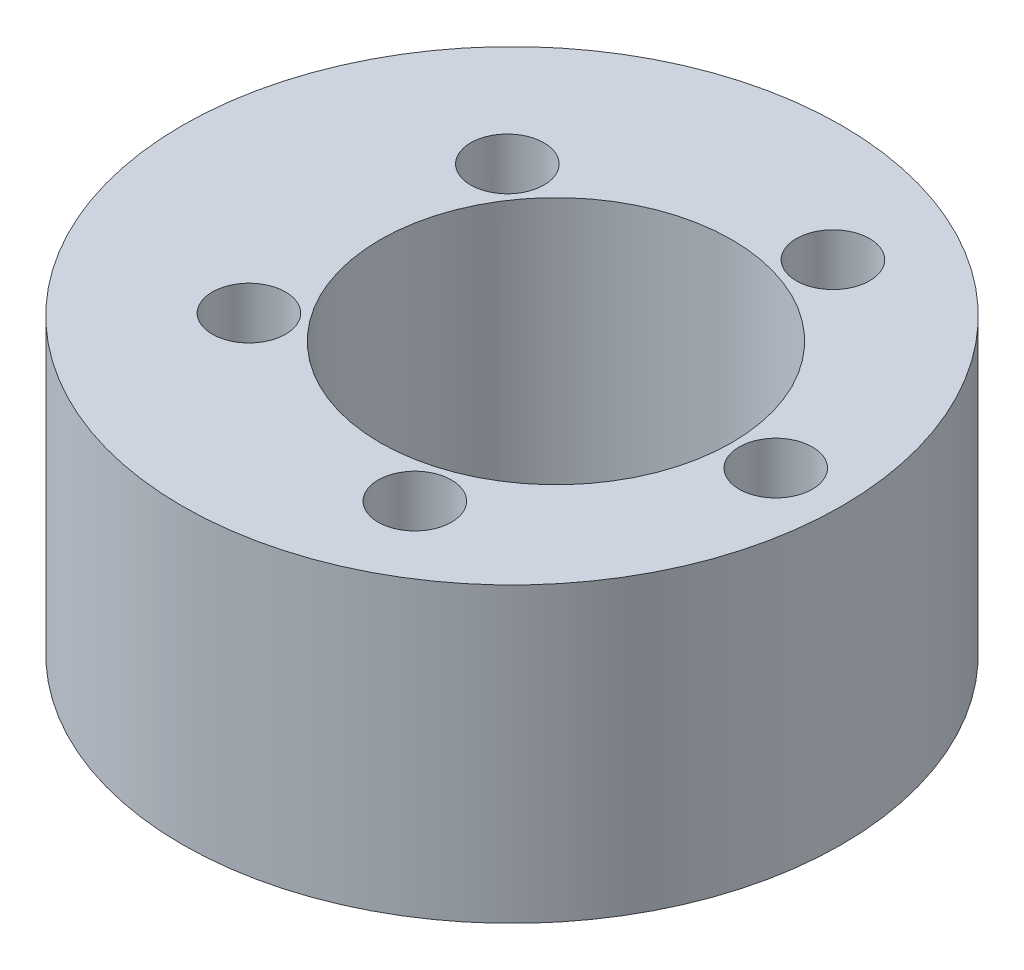
SolidWorks part; units mm, degrees
ref_plane "Front Plane" through (0, 0, 0) normal (0, 0, 1) x (1, 0, 0)
ref_plane "Top Plane" through (0, 0, 0) normal (0, 1, 0) x (1, 0, 0)
ref_plane "Right Plane" through (0, 0, 0) normal (1, 0, 0) x (0, 0, -1)
sketch "Sketch1" plane through (0, 0, 0) normal (0, 1, 0) x (1, 0, 0)
  line L0 (0, 0) -> (3, 0)
  line L1 (15, 0) -> (21, 0)
  circle A0 centre (0, 0) radius 22.5
  circle A1 centre (3, 0) radius 12
  circle A2 centre (3, 0) radius 18
  circle A3 centre (18, 0) radius 2.5
  circle A4 centre (7.6353, -14.2658) radius 2.5
  circle A5 centre (-9.1353, -8.8168) radius 2.5
  circle A6 centre (-9.1353, 8.8168) radius 2.5
  circle A7 centre (7.6353, 14.2658) radius 2.5
  point P11 (0, 0)
  point P20 (3, 0)
  dimension "D1" = 5
extrude "Boss-Extrude1" add sketch "Sketch1" along normal blind 20 contours A0 A1 | A2 | A1 | A5 | A7 | A6 | A3 | A4 region at (-21.8636, 0, 0)
sketch "Sketch2" plane through (0, 0, 0) normal (0, -1, 0) x (1, 0, 0)
  line L0 (0, 0) -> (3, 0)
  line L1 (15, 0) -> (21, 0)
  circle A0 centre (0, 0) radius 22.5
  circle A1 centre (3, 0) radius 12
  circle A2 centre (3, 0) radius 18
  circle A3 centre (18, 0) radius 2.5
  circle A4 centre (7.6353, -14.2658) radius 2.5
  circle A5 centre (-9.1353, -8.8168) radius 2.5
  circle A6 centre (-9.1353, 8.8168) radius 2.5
  circle A7 centre (7.6353, 14.2658) radius 2.5
  point P11 (0, 0)
  point P20 (3, 0)
  circle M12 centre (3, 0) radius 12
  circle M13 centre (-9.1353, 8.8168) radius 2.5
  circle M14 centre (7.6353, -14.2658) radius 2.5
  circle M15 centre (-9.1353, -8.8168) radius 2.5
  circle M16 centre (18, 0) radius 2.5
  circle M17 centre (7.6353, 14.2658) radius 2.5
  dimension "D1" = 5
extrude "Cut-Extrude1" cut sketch "Sketch2" against normal blind 3 contours A2 M16 M12 M13 M15 M17 M14 region at (-14.4909, 0, 0)
